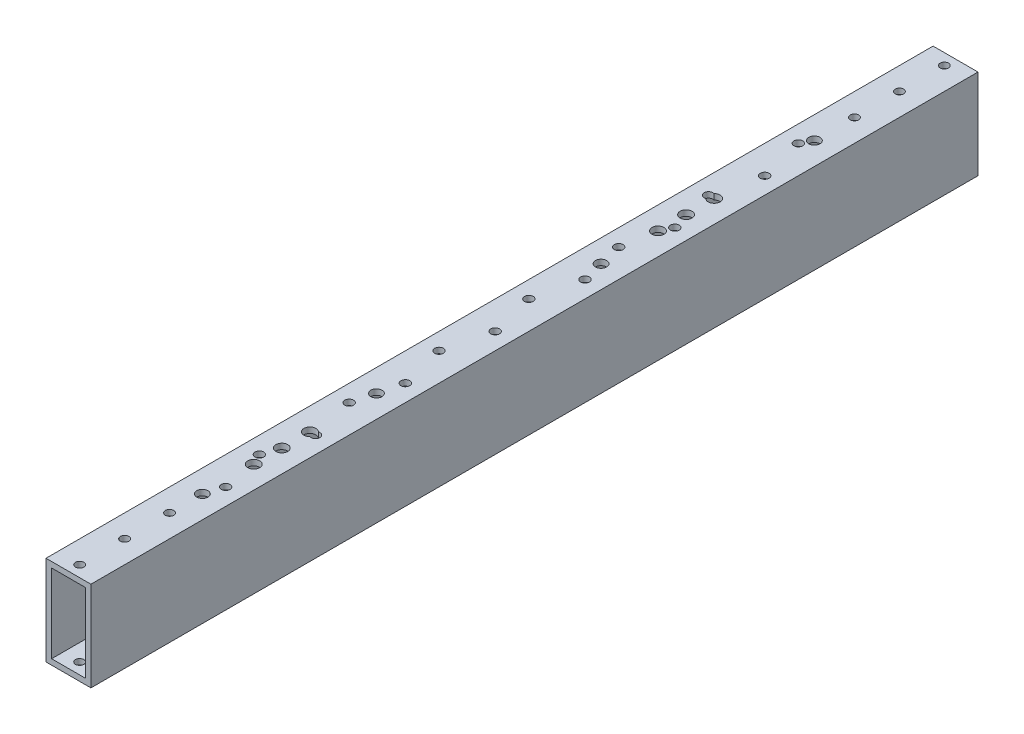
SolidWorks part; units mm, degrees
material "6061-T6 (SS)"
ref_plane "Front Plane" through (0, 0, 0) normal (0, 0, 1) x (1, 0, 0)
ref_plane "Top Plane" through (0, 0, 0) normal (0, 1, 0) x (1, 0, 0)
ref_plane "Right Plane" through (0, 0, 0) normal (1, 0, 0) x (0, 0, -1)
sketch "Sketch1" plane through (0, 0, 0) normal (0, 0, 1) x (1, 0, 0)
  line L1 (-12.7, -25.4) -> (12.7, -25.4)
  line L2 (-12.7, -25.4) -> (-12.7, 25.4)
  line L3 (-12.7, 25.4) -> (12.7, 25.4)
  line L4 (12.7, -25.4) -> (12.7, 25.4)
  line L5 (-12.7, -25.4) -> (12.7, 25.4) construction
  line L6 (-12.7, 25.4) -> (12.7, -25.4) construction
  point P0 (0, 0)
  dimension "D1" = 50.8
  dimension "D2" = 25.4
extrude "Extrude-Thin1" add sketch "Sketch1" along normal blind 501.65 thin thin type one direction reverse wall 3.175
hole_wizard "3/16 (0.1875) Diameter Hole1" positions "3DSketch1" profile "Sketch3" hole size "3/16" standard "ANSI Inch" end condition through all
sketch3d "3DSketch1"
  line L1 (12.7, 25.4, 0) -> (-12.7, 25.4, 0) construction
  line L6 (0, 25.4, 501.65) -> (0, 25.4, 0) construction
  line L7 (12.7, 25.4, 501.65) -> (-12.7, 25.4, 501.65) construction
  point P57 (0, 25.4, 6.35)
  point P59 (0, 25.4, 31.75)
  point P61 (0, 25.4, 57.15)
  point P63 (0, 25.4, 469.9)
  point P65 (0, 25.4, 444.5)
  point P67 (0, 25.4, 495.3)
  dimension "D1" = 25.4
  dimension "D2" = 25.4
  dimension "D3" = 6.35
  dimension "D4" = 25.4
  dimension "D5" = 25.4
  dimension "D6" = 6.35
sketch "Sketch3" plane through (0, 25.4, 495.3) normal (1, 0, 0) x (0, 0, 1)
  line L0 (0, 0) -> (0, 50.8)
  line L1 (0, 50.8) -> (2.3812, 50.8)
  line L2 (2.3812, 50.8) -> (2.3812, 0)
  line L5 (2.3812, 0) -> (0, 0)
  line L11 (0, -6.35) -> (0, 107.95) construction
  dimension "Thru Hole Dia." = 4.7625
  dimension "Thru Hole Depth" = 50.8
hole_wizard "1/4 (0.25) Diameter Hole1" positions "Sketch7" profile "Sketch6" hole size "1/4" standard "ANSI Inch"
sketch "Sketch7" plane through (0, 25.4, 0) normal (0, 1, 0) x (1, 0, 0)
  point P6 (0, -79.831)
  point P9 (0, -425.9339)
  point P23 (0, -327.499)
  point P26 (0, -200.481)
sketch "Sketch6" plane through (0, 25.4, 79.831) normal (1, 0, 0) x (0, 0, 1)
  line L0 (0, 0) -> (0, 27.3077)
  line L1 (0, 27.3077) -> (3.175, 25.4)
  line L2 (3.175, 25.4) -> (3.175, 0)
  line L5 (3.175, 0) -> (0, 0)
  line L10 (0, 27.3077) -> (-3.175, 25.4) construction
  line L11 (0, -6.35) -> (0, 107.95) construction
  dimension "Hole Dia." = 6.35
  dimension "Hole Depth" = 25.4
  dimension "Drill Angle" = 118
hole_wizard "1/4 Clearance Hole1" positions "Sketch8" profile "Sketch9" hole size "1/4" standard "ANSI Inch"
sketch "Sketch8" plane through (381, 25.4, 250.825) normal (0, 1, 0) x (1, 0, 0)
  point P0 (381, 82.55)
  point P3 (381, 98.425)
  point P6 (381, 114.3)
  point P9 (381, -146.05)
  point P12 (381, -130.175)
  point P15 (381, -114.3)
  point P18 (-381, -146.05)
  point P21 (-381, -130.175)
  point P24 (-381, -114.3)
  point P27 (-381, 82.55)
  point P30 (-381, 98.425)
  point P33 (-381, 114.3)
sketch "Sketch9" plane through (762, 25.4, 168.275) normal (1, 0, 0) x (0, 0, 1)
  line L0 (0, 0) -> (0, 40.1298)
  line L1 (0, 40.1298) -> (3.3782, 38.1)
  line L2 (3.3782, 38.1) -> (3.3782, 0)
  line L3 (3.3782, 0) -> (0, 0)
  line L4 (0, 40.1298) -> (-3.3782, 38.1) construction
  line L5 (0, -6.35) -> (0, 107.95) construction
  dimension "Hole Dia." = 6.7564
  dimension "Hole Depth" = 38.1
  dimension "Drill Angle" = 118
hole_wizard "3/16 (0.195) Diameter Hole1" positions "Sketch10" profile "Sketch11" hole size "3/16" standard "ANSI Inch" end condition through all
sketch "Sketch10" plane through (0, -25.4, 0) normal (0, -1, 0) x (-1, 0, 0)
  point P0 (3.1693, -85.725)
  point P3 (-3.1807, -111.125)
  point P6 (3.1693, -136.525)
  point P9 (-3.1807, -161.925)
  point P12 (3.1693, -187.325)
  point P15 (-3.1807, -212.725)
  point P18 (3.1693, -238.125)
  point P21 (-3.1807, -263.525)
  point P24 (3.1693, -288.925)
  point P27 (-3.1807, -314.325)
  point P30 (3.1693, -339.725)
  point P33 (-3.1807, -365.125)
  point P36 (3.1693, -390.525)
  point P39 (-3.1807, -415.925)
sketch "Sketch11" plane through (-3.1693, -25.4, 85.725) normal (1, 0, 0) x (0, 0, -1)
  line L0 (0, 0) -> (0, 50.8)
  line L1 (0, 50.8) -> (2.4765, 50.8)
  line L2 (2.4765, 50.8) -> (2.4765, 0)
  line L5 (2.4765, 0) -> (0, 0)
  line L11 (0, -6.35) -> (0, 107.95) construction
  dimension "Thru Hole Dia." = 4.953
  dimension "Thru Hole Depth" = 50.8
